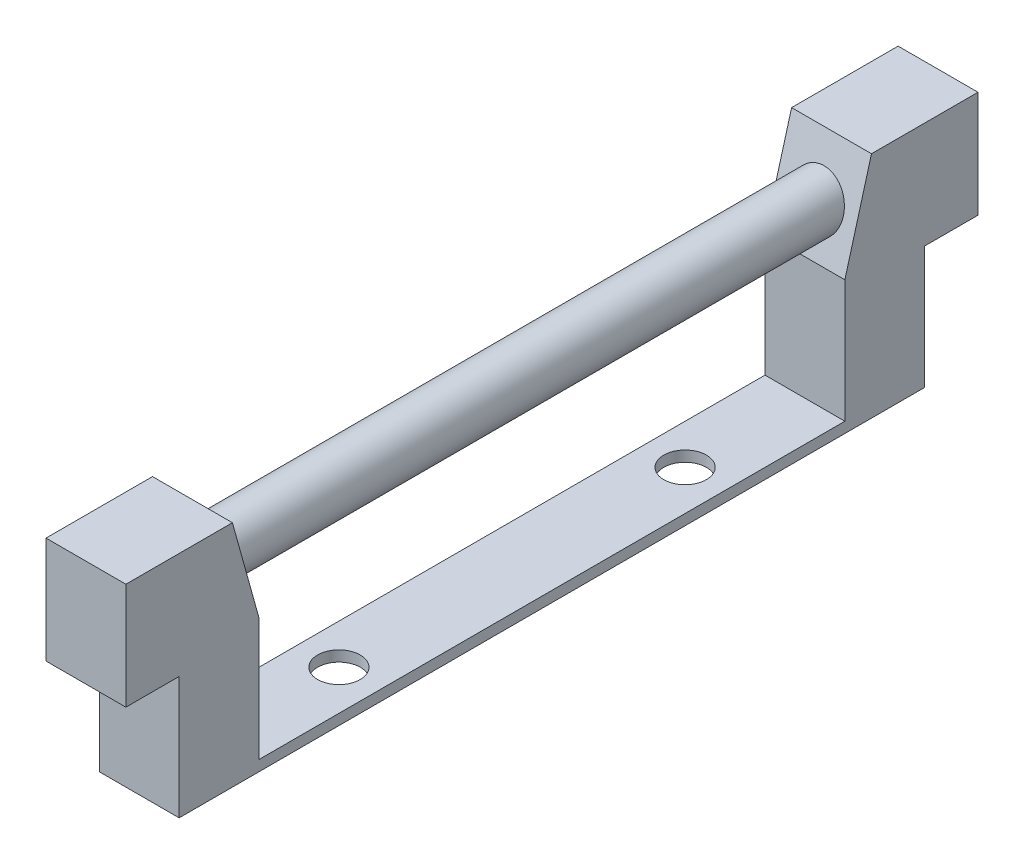
SolidWorks part; units mm, degrees
ref_plane "Front Plane" through (0, 0, 0) normal (0, 0, 1) x (1, 0, 0)
ref_plane "Top Plane" through (0, 0, 0) normal (0, 1, 0) x (1, 0, 0)
ref_plane "Right Plane" through (0, 0, 0) normal (1, 0, 0) x (0, 0, -1)
sketch "Sketch1" plane through (0, 0, 0) normal (1, 0, 0) x (0, 0, -1)
  line L0 (-60, 0) -> (60, 0) construction
  line L1 (-55, -18) -> (-60, 0)
  line L2 (-60, 0) -> (-80, 0)
  line L3 (-80, 0) -> (-80, -20)
  line L4 (-80, -20) -> (-70, -20)
  line L5 (-70, -20) -> (-70, -43)
  line L6 (-70, -43) -> (-55, -43)
  line L7 (-55, -43) -> (-55, -18)
  line L8 (0, 0) -> (0, -93.1995) construction
  line L9 (55, -43) -> (55, -18)
  line L10 (70, -43) -> (55, -43)
  line L11 (70, -20) -> (70, -43)
  line L12 (80, -20) -> (70, -20)
  line L13 (80, 0) -> (80, -20)
  line L14 (60, 0) -> (80, 0)
  line L15 (55, -18) -> (60, 0)
  line L17 (-55, -43) -> (55, -43)
  line L18 (-55, -43) -> (-55, -41)
  line L19 (-55, -41) -> (55, -41)
  line L20 (55, -43) -> (55, -41)
  dimension "D1" = 20
  dimension "D2" = 15
  dimension "D3" = 43
  dimension "D4" = 20
  dimension "D5" = 10
  dimension "D6" = 120
  dimension "D7" = 25
  dimension "D8" = 2
extrude "Boss-Extrude1" add sketch "Sketch1" along normal blind 7.5 and the other way blind 7.5 contours L6 L7 L1 L2 L3 L4 L5 | L15 L9 L10 L11 L12 L13 L14 | L19 L7 L17 L9 region at (0, -19.4969, 65.9531) region at (0, -42, 0) region at (0, -19.4969, -65.9531)
sketch "Sketch2" plane through (0, 0, 0) normal (0, 0, 1) x (1, 0, 0)
  line L0 (0, 0) -> (0, -20) construction
  line L1 (-7.5, -20) -> (7.5, -20) construction
  circle A0 centre (0, -10) radius 5
  dimension "D1" = 10
extrude "Boss-Extrude2" add sketch "Sketch2" against normal blind 60 and the other way blind 60
sketch "Sketch3" plane through (0, -41, 0) normal (0, 1, 0) x (1, 0, 0)
  line L0 (0, 32.5) -> (0, -32.5) construction
  circle A0 centre (0, 32.5) radius 4
  circle A1 centre (0, -32.5) radius 4
  dimension "D2" = 8
  dimension "D1" = 65
extrude "Cut-Extrude1" cut sketch "Sketch3" against normal blind 60
